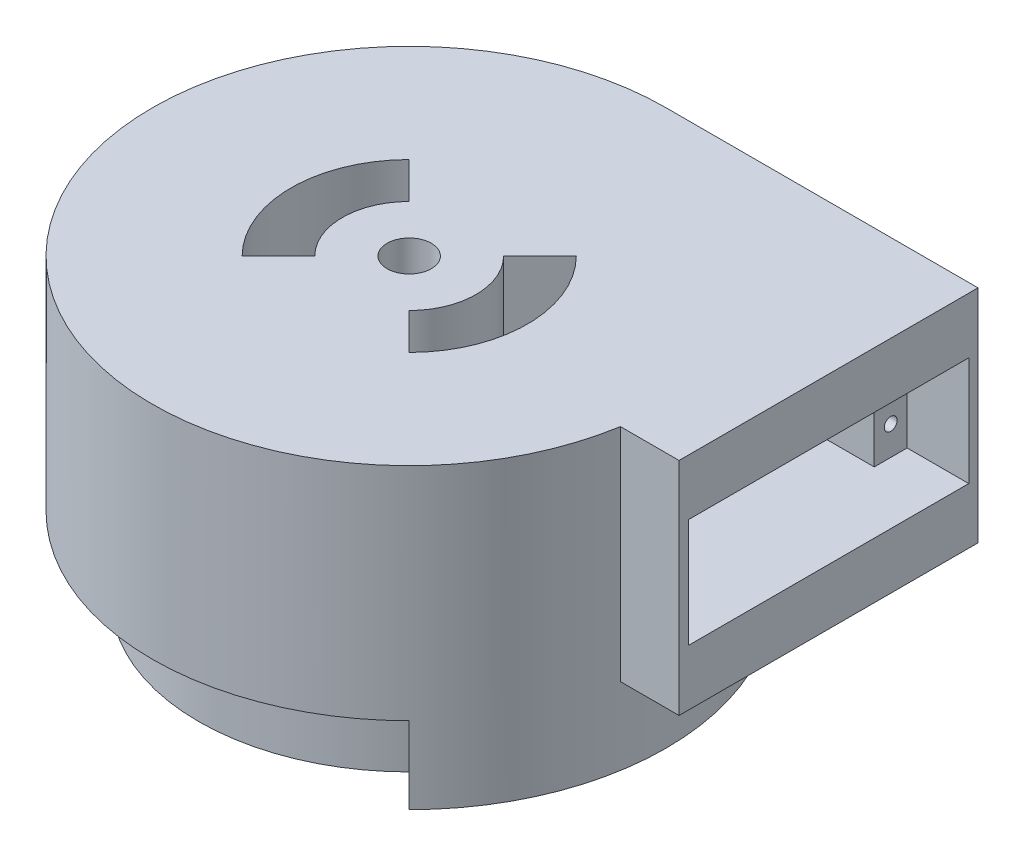
SolidWorks part; units mm, degrees
ref_plane "Front Plane" through (0, 0, 0) normal (0, 0, 1) x (1, 0, 0)
ref_plane "Top Plane" through (0, 0, 0) normal (0, 1, 0) x (1, 0, 0)
ref_plane "Right Plane" through (0, 0, 0) normal (1, 0, 0) x (0, 0, -1)
sketch "Sketch1" plane through (0, 0, 0) normal (0, 1, 0) x (1, 0, 0)
  line L0 (0, 50) -> (60.7381, 50)
  line L1 (60.7381, 50) -> (60.7381, -8.2)
  line L2 (60.7381, -8.2) -> (49.323, -8.2)
  line L3 (0, 60.3307) -> (0, -56.6529) construction
  arc A0 (0, 50) -> (49.323, -8.2) centre (0, 0) ccw
  dimension "D2" = 50
  dimension "D7" = 58.2
extrude "Boss-Extrude1" add sketch "Sketch1" along normal blind 43
sketch "Sketch4" plane through (0, 0, 0) normal (0, -1, 0) x (1, 0, 0)
  line L0 (-50, 0) -> (60.7381, 0) construction
  line L1 (60.7381, 8.2) -> (60.7381, -50) construction
  line L2 (28.9914, 28.9914) -> (35.3553, 35.3553)
  line L3 (28.9914, -28.9914) -> (35.3553, -35.3553)
  line L4 (28.9914, -28.9914) -> (0, 0) construction
  line L5 (0, 0) -> (28.9914, 28.9914) construction
  arc A0 (49.323, 8.2) -> (0, -50) centre (0, 0) ccw construction
  arc A1 (28.9914, 28.9914) -> (28.9914, -28.9914) centre (0, 0) ccw
  arc A4 (35.3553, -35.3553) -> (35.3553, 35.3553) centre (0, 0) ccw
  dimension "D1" = 45
  dimension "D2" = 45
  dimension "D3" = 9
extrude "Boss-Extrude2" add sketch "Sketch4" along normal blind 15
sketch "Sketch5" plane through (60.7381, 0, 0) normal (1, 0, 0) x (0, 0, -1)
  line L0 (20.9, 43) -> (20.9, 0) construction
  line L1 (-8.2, 43) -> (50, 43) construction
  line L2 (-8.2, 0) -> (50, 0) construction
  line L3 (-8.2, 21.5) -> (50, 21.5) construction
  line L4 (-8.2, 43) -> (-8.2, 0) construction
  line L5 (50, 43) -> (50, 0) construction
  line L6 (-3.2, 26.45) -> (-3.2, 16.55) construction
  line L7 (0.6, 11.5) -> (41.2, 11.5) construction
  line L8 (0.6, 11.5) -> (0.6, 31.5) construction
  line L9 (0.6, 31.5) -> (41.2, 31.5) construction
  line L10 (41.2, 11.5) -> (41.2, 31.5) construction
  line L11 (0.6, 11.5) -> (41.2, 31.5) construction
  line L12 (0.6, 31.5) -> (41.2, 11.5) construction
  line L13 (45, 26.45) -> (45, 16.55) construction
  line L14 (0, 10.9) -> (0, 32.1)
  line L15 (0, 32.1) -> (41.8, 32.1)
  line L16 (41.8, 32.1) -> (41.8, 10.9)
  line L17 (41.8, 10.9) -> (0, 10.9)
  line L18 (0, 10.9) -> (-6.4, 10.9)
  line L19 (-6.4, 10.9) -> (-6.4, 32.1)
  line L20 (-6.4, 32.1) -> (0, 32.1)
  line L21 (41.8, 32.1) -> (48.2, 32.1)
  line L22 (48.2, 32.1) -> (48.2, 10.9)
  line L23 (48.2, 10.9) -> (41.8, 10.9)
  circle A0 centre (-3.2, 26.45) radius 1.25
  circle A1 centre (-3.2, 16.55) radius 1.25
  circle A2 centre (45, 16.55) radius 1.25
  circle A3 centre (45, 26.45) radius 1.25
  circle A4 centre (31, 21.5) radius 6 construction
  point P12 (20.9, 21.5)
  point P25 (-3.2, 21.5)
  point P27 (45, 21.5)
  point P38 (20.9, 32.1)
  point P39 (-6.4, 21.5)
  dimension "D8" = 2.5
  dimension "D9" = 2.5
  dimension "D10" = 2.5
  dimension "D11" = 2.5
  dimension "D14" = 12
  dimension "D13" = 17.2
  dimension "D1" = 9.9
  dimension "D2" = 9.9
  dimension "D3" = 24.1
  dimension "D4" = 24.1
  dimension "D5" = 0.6
  dimension "D6" = 20
  dimension "D7" = 54.6
  dimension "D12" = 0.6
extrude "Cut-Extrude1" cut sketch "Sketch5" against normal blind 40 contours L17 L16 L15 L14 region at (60.7381, 21.5, -20.9)
extrude "Cut-Extrude2" cut sketch "Sketch5<5>" against normal blind 12 contours L20 L19 L18 L14 A1 A0 | L23 L22 L21 L16 A3 A2 region at (60.7381, 21.5, 3.2) region at (60.7381, 21.5, -45)
sketch "Sketch5<5>" plane through (60.7381, 0, 0) normal (1, 0, 0) x (0, 0, -1) same geometry as "Sketch5"
extrude "Cut-Extrude3" cut sketch "Sketch5<6>" against normal blind 50 contours A3 | A2 | A0 | A1 region at (60.7381, 26.45, 3.2) region at (60.7381, 16.55, 3.2) region at (60.7381, 16.55, -45) region at (60.7381, 26.45, -45)
sketch "Sketch5<6>" plane through (60.7381, 0, 0) normal (1, 0, 0) x (0, 0, -1) same geometry as "Sketch5"
sketch "Sketch6" plane through (0, -15, 0) normal (0, -1, 0) x (1, 0, 0)
  line L0 (0, -50) -> (0, 50) construction
  line L1 (50, 0) -> (-50, 0) construction
  line L2 (9.1924, 9.1924) -> (16.2635, 16.2635)
  line L3 (9.1924, -9.1924) -> (16.2635, -16.2635)
  line L4 (0, 0) -> (9.1924, 9.1924) construction
  line L5 (9.1924, -9.1924) -> (0, 0) construction
  line L6 (-9.1924, -9.1924) -> (-16.2635, -16.2635)
  line L7 (-9.1924, 9.1924) -> (-16.2635, 16.2635)
  circle A0 centre (0, 0) radius 4.3
  arc A1 (35.3553, 35.3553) -> (0, -50) centre (0, 0) ccw construction
  arc A2 (35.3553, -35.3553) -> (35.3553, 35.3553) centre (0, 0) ccw construction
  arc A3 (9.1924, 9.1924) -> (9.1924, -9.1924) centre (0, 0) cw
  arc A4 (16.2635, -16.2635) -> (16.2635, 16.2635) centre (0, 0) ccw
  arc A5 (-16.2635, -16.2635) -> (-16.2635, 16.2635) centre (0, 0) cw
  arc A6 (-9.1924, 9.1924) -> (-9.1924, -9.1924) centre (0, 0) ccw
  point P19 (13.476, -16.1058)
  dimension "D1" = 8.6
  dimension "D3" = 10
  dimension "D4" = 13
  dimension "D2" = 45
  dimension "D5" = 45
extrude "Cut-Extrude4" cut sketch "Sketch6" against normal through all both and the other way through all
sketch "Sketch7" plane through (48.7381, 0, 0) normal (1, 0, 0) x (0, 0, -1)
  line L0 (41.8, 32.1) -> (41.8, 10.9) construction
  line L1 (36.8, 18.1) -> (46.8, 18.1)
  line L2 (36.8, 18.1) -> (36.8, 24.9)
  line L3 (36.8, 24.9) -> (46.8, 24.9)
  line L4 (46.8, 18.1) -> (46.8, 24.9)
  line L5 (36.8, 18.1) -> (46.8, 24.9) construction
  line L6 (36.8, 24.9) -> (46.8, 18.1) construction
  point P0 (41.8, 21.5)
  dimension "D1" = 6.8
  dimension "D2" = 10
extrude "Cut-Extrude5" cut sketch "Sketch7" against normal through all from offset 5 offset against normal yes
